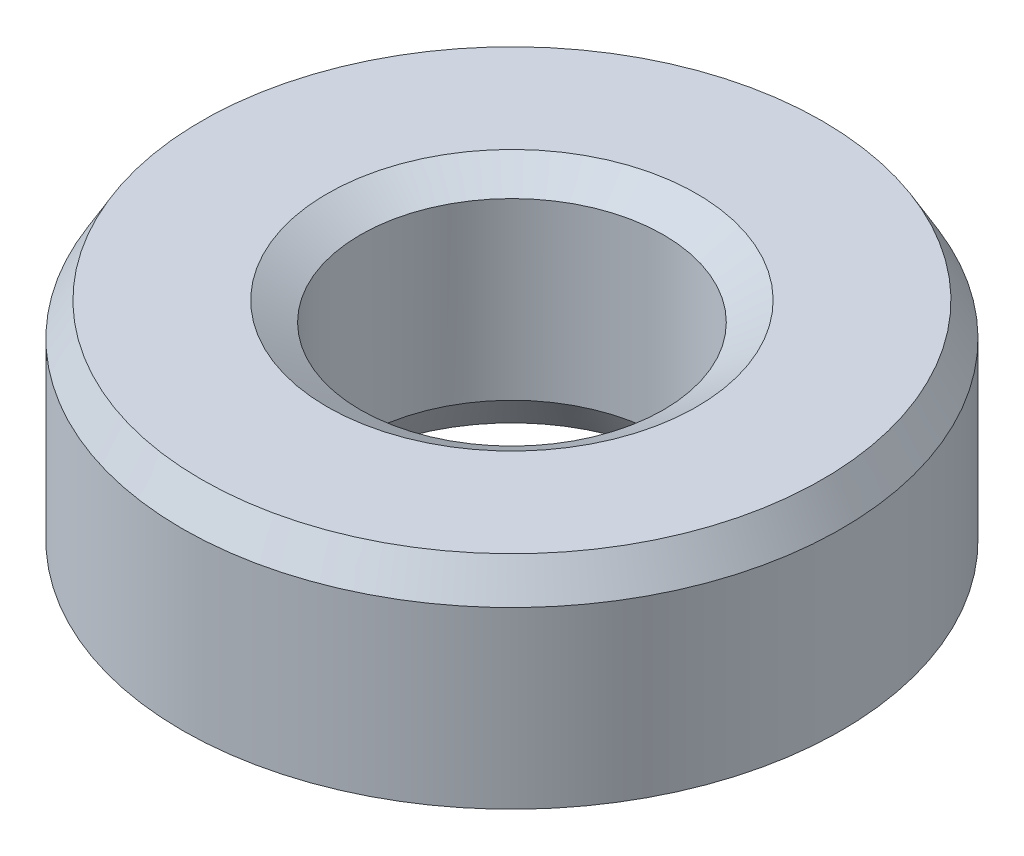
SolidWorks part; units mm, degrees
ref_plane "Front Plane" through (0, 0, 0) normal (0, 0, 1) x (1, 0, 0)
ref_plane "Top Plane" through (0, 0, 0) normal (0, 1, 0) x (1, 0, 0)
ref_plane "Right Plane" through (0, 0, 0) normal (1, 0, 0) x (0, 0, -1)
sketch "Sketch1" plane through (0, 0, 0) normal (0, 1, 0) x (1, 0, 0)
  circle A0 centre (0, 0) radius 17.5
  dimension "SLEEVE_OD" = 35
extrude "Boss-Extrude1" add sketch "Sketch1" along normal blind 12.0488
sketch "Sketch2" plane through (0, 0, 0) normal (0, 1, 0) x (1, 0, 0)
  circle A0 centre (0, 0) radius 8.0499
  dimension "BORE_D" = 16.0997
extrude "Cut-Extrude1" cut sketch "Sketch2" along normal through all
chamfer "Chamfer1" distance 1.7586 angle 30 4 edges at (0, 12.0488, 8.0499) (0, 0, 8.0499) (0, 0, 17.5) (0, 12.0488, 17.5) first distance on face at (0, 12.0488, 8.0499) first distance on face at (0, 0, 8.0499) first distance on face at (0, 12.0488, 17.5)
